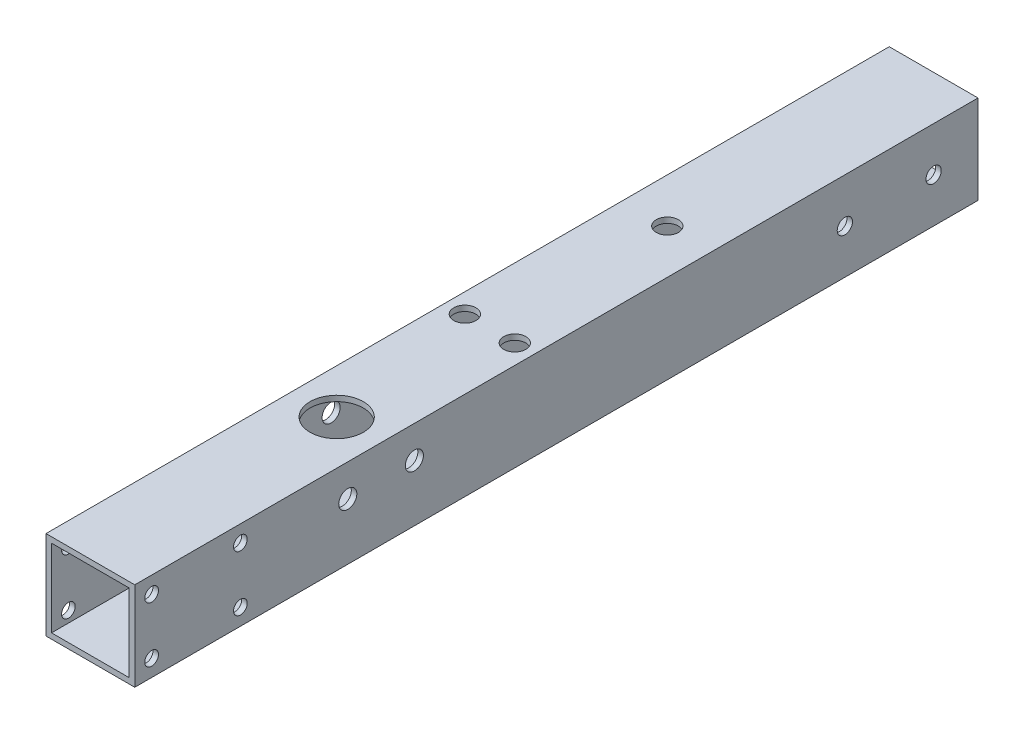
SolidWorks part; units mm, degrees
material "Acrylic (Medium-high impact)"
ref_plane "Front Plane" through (0, 0, 0) normal (0, 0, 1) x (1, 0, 0)
ref_plane "Top Plane" through (0, 0, 0) normal (0, 1, 0) x (1, 0, 0)
ref_plane "Right Plane" through (0, 0, 0) normal (1, 0, 0) x (0, 0, -1)
sketch "Sketch1" plane through (0, 0, 0) normal (0, 0, 1) x (1, 0, 0)
  line L1 (-12.7, 12.7) -> (12.7, 12.7)
  line L2 (-12.7, 12.7) -> (-12.7, -12.7)
  line L3 (-12.7, -12.7) -> (12.7, -12.7)
  line L4 (12.7, 12.7) -> (12.7, -12.7)
  line L5 (-12.7, 12.7) -> (12.7, -12.7) construction
  line L6 (-12.7, -12.7) -> (12.7, 12.7) construction
  line L7 (-11.1125, 11.1125) -> (11.1125, 11.1125)
  line L8 (-11.1125, 11.1125) -> (-11.1125, -11.1125)
  line L9 (-11.1125, -11.1125) -> (11.1125, -11.1125)
  line L10 (11.1125, 11.1125) -> (11.1125, -11.1125)
  line L11 (-11.1125, 11.1125) -> (11.1125, -11.1125) construction
  line L12 (-11.1125, -11.1125) -> (11.1125, 11.1125) construction
  point P0 (0, 0)
  point P6 (0, 0)
  dimension "D1" = 25.4
  dimension "D2" = 25.4
  dimension "D3" = 22.225
extrude "Boss-Extrude1" add sketch "Sketch1" along normal blind 241.3
sketch "Sketch7" plane through (0, 12.7, 0) normal (0, 1, 0) x (1, 0, 0)
  line L0 (12.7, 0) -> (-12.7, 0) construction
  line L1 (-9.1281, -127) -> (9.1281, -127) construction
  line L4 (12.7, -76.2) -> (-12.7, -76.2) construction
  line L5 (12.7, -241.3) -> (12.7, 0) construction
  line L6 (-12.7, -241.3) -> (-12.7, 0) construction
  circle A0 centre (0, -76.2) radius 1.9844
  circle A2 centre (7.1437, -127) radius 1.9844
  circle A3 centre (-7.1438, -127) radius 1.9844
  circle A4 centre (-7.1438, -127) radius 3.175
  circle A5 centre (7.1437, -127) radius 3.175
  circle A6 centre (0, -76.2) radius 3.175
  point P13 (0, -127)
  dimension "D3" = 3.9688
  dimension "D2" = 127
  dimension "D5" = 6.35
  dimension "D1" = 50.8
  dimension "D4" = 14.2875
extrude "Cut-Extrude8" cut sketch "Sketch7" against normal through all contours A3 | A2 | A0 region at (0, 12.7, 76.2) region at (7.1437, 12.7, 127) region at (-7.1438, 12.7, 127)
sketch "Sketch10" plane through (-12.7, 0, 0) normal (-1, 0, 0) x (0, 0, 1)
  line L0 (0, 12.7) -> (0, -12.7) construction
  circle A0 centre (12.7, 0) radius 2.1828
  circle A1 centre (38.1, 0) radius 2.1828
  point P6 (0, 0)
  dimension "D1" = 4.3656
  dimension "D3" = 12.7
  dimension "D4" = 25.4
extrude "Cut-Extrude7" cut sketch "Sketch10" against normal up to surface (25.4 mm away) up to face at (12.7, 0, 120.65)
extrude "Cut-Extrude9" cut sketch "Sketch7<5>" against normal up to surface (1.5875 mm away) up to face at (-7.1438, 11.1125, 125.0156)
sketch "Sketch7<5>" plane through (0, 12.7, 0) normal (0, 1, 0) x (1, 0, 0) same geometry as "Sketch7"
sketch "Sketch13" plane through (-12.7, 0, 0) normal (-1, 0, 0) x (0, 0, 1)
  line L0 (241.3, 12.7) -> (0, 12.7) construction
  line L4 (0, 12.7) -> (0, -12.7)
  line L5 (0, -12.7) -> (241.3, -12.7)
  line L6 (241.3, -12.7) -> (241.3, 12.7)
  line L7 (241.3, 12.7) -> (0, 12.7)
  line L8 (0, 12.7) -> (0, -12.7)
  line L9 (0, -12.7) -> (241.3, -12.7)
  line L10 (241.3, -12.7) -> (241.3, 12.7)
  line L11 (241.3, 12.7) -> (0, 12.7)
  circle A1 centre (161.29, 3.4925) radius 2.5908
  circle A3 centre (180.34, 3.4925) radius 2.5908
  dimension "D3" = 60.96
  dimension "D4" = 9.2075
  dimension "D5" = 5.1816
  dimension "D2" = 19.05
  dimension "D1" = 0
extrude "Cut-Extrude10" cut sketch "Sketch13" against normal through all contours A1 | A3
sketch "Sketch14" plane through (0, 12.7, 0) normal (0, 1, 0) x (1, 0, 0)
  line L1 (12.7, -241.3) -> (-12.7, -241.3) construction
  line L2 (12.7, -241.3) -> (12.7, 0) construction
  circle A0 centre (0, -170.815) radius 7.62
  dimension "D1" = 15.24
  dimension "D2" = 70.485
  dimension "D3" = 12.7
extrude "Cut-Extrude11" cut sketch "Sketch14" against normal up to next
sketch "Sketch16" plane through (12.7, 0, 0) normal (1, 0, 0) x (0, 0, -1)
  line L0 (-241.3, -12.7) -> (-241.3, 12.7) construction
  line L2 (-241.3, 12.7) -> (0, 12.7) construction
  line L3 (-241.3, -12.7) -> (0, -12.7) construction
  circle A0 centre (-236.474, -7.9375) radius 1.9558
  circle A1 centre (-236.474, 7.9375) radius 1.9558
  circle A2 centre (-211.074, -7.9375) radius 1.9558
  circle A3 centre (-211.074, 7.9375) radius 1.9558
  dimension "D1" = 3.9116
  dimension "D2" = 4.826
  dimension "D3" = 25.4
  dimension "D4" = 4.7625
  dimension "D5" = 4.7625
extrude "Cut-Extrude12" cut sketch "Sketch16" against normal through all
